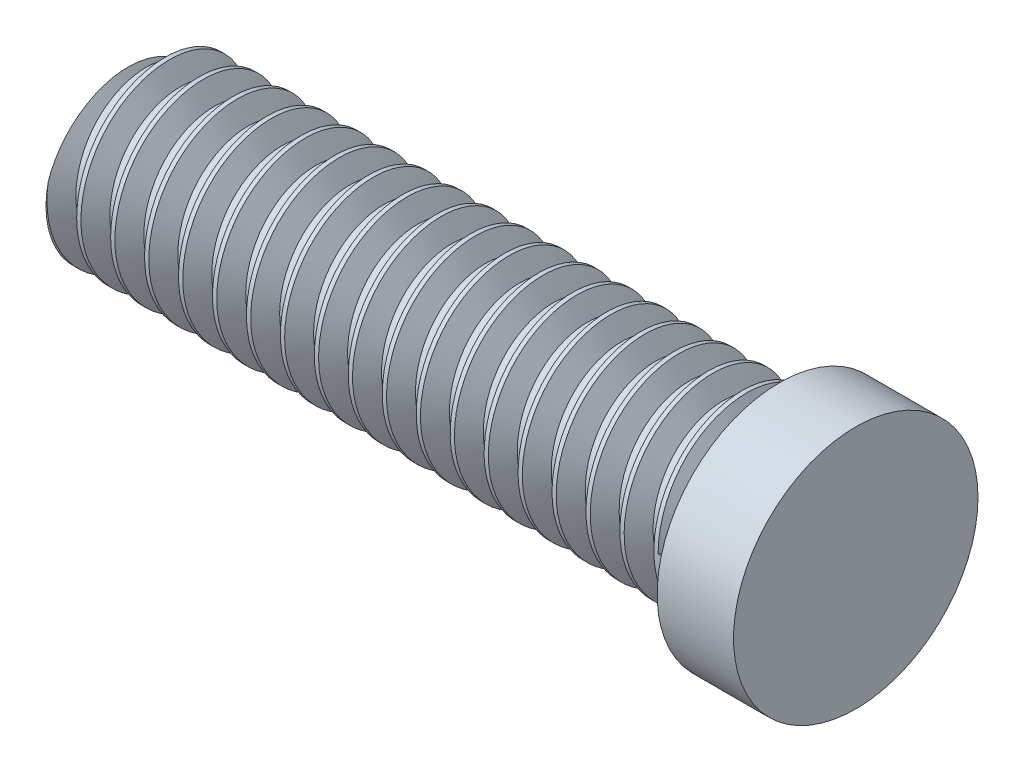
SolidWorks part; units mm, degrees
ref_plane "Front Plane" through (0, 0, 0) normal (0, 0, 1) x (1, 0, 0)
ref_plane "Top Plane" through (0, 0, 0) normal (0, 1, 0) x (1, 0, 0)
ref_plane "Right Plane" through (0, 0, 0) normal (1, 0, 0) x (0, 0, -1)
sketch "Sketch1" plane through (0, 0, 0) normal (1, 0, 0) x (0, 0, -1)
  circle A0 centre (0, 0) radius 1.905
  point P3 (0, 0)
  dimension "D1" = 3.81
extrude "Boss-Extrude1" add sketch "Sketch1" along normal blind 13.335
sketch "Sketch2" plane through (13.335, 0, 0) normal (1, 0, 0) x (0, 0, -1)
  circle A0 centre (0, 0) radius 2.54
  dimension "D1" = 5.08
extrude "Boss-Extrude2" add sketch "Sketch2" along normal blind 1.5875
thread "Thread1" pitch 0.7056 method cut profile "Thread Profile1" start angle 3, offset 0, length 15.24, pitch 0.7056, diameter 3.81
ref_plane "Plane1" through (13.335, 0.0997, 1.9024) normal (0, -0.9986, 0.0523) x (0, 0.0523, 0.9986)
sketch "Thread Profile1" plane through (13.335, 0.0997, 1.9024) normal (0, -0.9986, 0.0523) x (0, 0.0523, 0.9986)
  line L0 (0, 0) -> (0, 0.7056) construction
  line L11 (0, 0) -> (0, 0.6174)
  line L12 (0, 0.6174) -> (-0.3819, 0.3969)
  line L13 (-0.3819, 0.3969) -> (-0.3819, 0.2205)
  line L15 (-0.3819, 0.2205) -> (0, 0)
  line L17 (-0.3819, 0.3087) -> (0, 0.3087) construction
  point P2 (0, 0)
  dimension "Pitch" = 0.7056
  dimension "Profile_Angle" = 60
  dimension "Profile_Land" = 0.1764
  dimension "Profile_Height" = 0.3819
ref_axis "Axis1" through (13.4429, 0, 0) along (-1, 0, 0)
